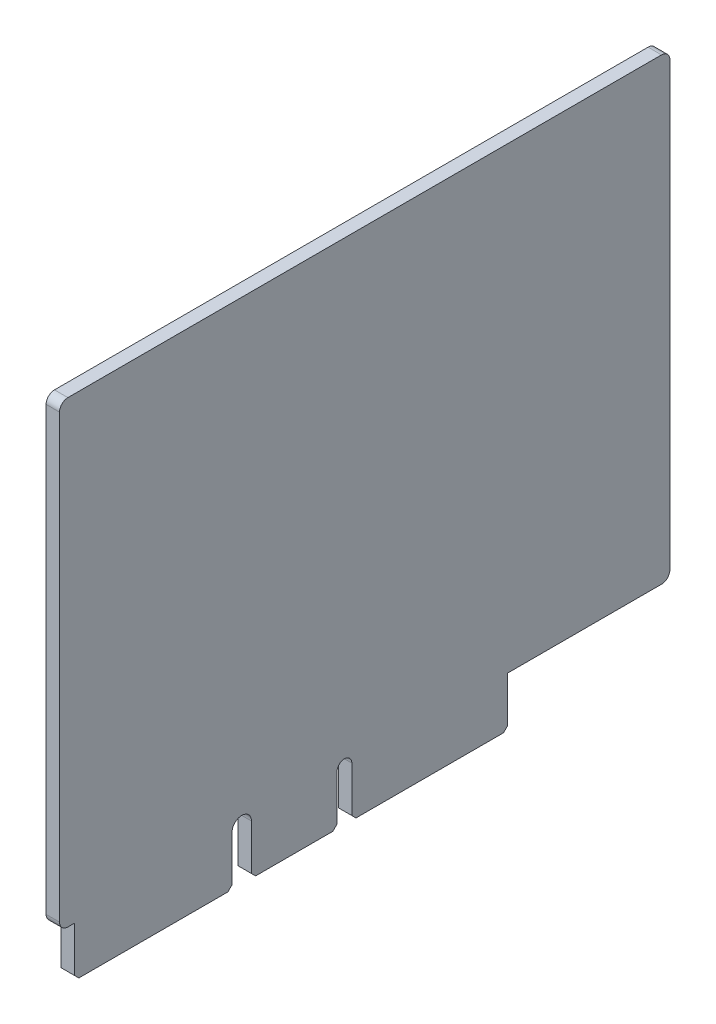
SolidWorks part; units mm, degrees
ref_plane "Front Plane" through (0, 0, 0) normal (0, 0, 1) x (1, 0, 0)
ref_plane "Top Plane" through (0, 0, 0) normal (0, 1, 0) x (1, 0, 0)
ref_plane "Right Plane" through (0, 0, 0) normal (1, 0, 0) x (0, 0, -1)
ref_plane "Plane1" through (23.8249, 0, 0) normal (1, 0, 0) x (0, 0, -1)
sketch "Sketch2" plane through (23.8249, 0, 0) normal (1, 0, 0) x (0, 0, -1)
  line L0 (-11.1377, 57.2752) -> (-31.2577, 57.2752) construction
  line L1 (-65.4077, 112.0173) -> (7.4736, 112.0173)
  line L2 (-65.4077, 112.0173) -> (-65.4077, 57.2752)
  line L3 (-65.4077, 57.2752) -> (-63.6027, 57.2752)
  line L4 (7.4736, 112.0173) -> (7.4736, 57.2752)
  line L5 (-44.8027, 57.2752) -> (-42.4927, 57.2752) construction
  line L6 (-32.2677, 57.2752) -> (-30.5077, 57.2752) construction
  line L7 (-11.8877, 57.2752) -> (7.4736, 57.2752)
  line L8 (-63.6027, 51.8452) -> (-63.1027, 51.3452)
  line L9 (-44.8027, 51.3452) -> (-44.8027, 56.5252)
  line L10 (-44.8027, 56.5252) -> (-63.6027, 56.5252)
  line L11 (-63.6027, 56.5252) -> (-63.6027, 51.3452)
  line L12 (-63.6027, 51.3452) -> (-44.8027, 51.3452)
  line L13 (-44.8027, 51.8452) -> (-44.8027, 57.2752)
  line L15 (-63.6027, 57.2752) -> (-63.6027, 51.8452)
  line L16 (-63.1027, 51.3452) -> (-45.3027, 51.3452)
  line L17 (-32.2677, 51.3452) -> (-32.2677, 56.5252)
  line L18 (-32.2677, 56.5252) -> (-42.4927, 56.5252)
  line L19 (-42.4927, 56.5252) -> (-42.4927, 51.3452)
  line L20 (-42.4927, 51.3452) -> (-32.2677, 51.3452)
  line L21 (-32.2677, 51.8452) -> (-32.2677, 57.2752)
  line L23 (-42.4927, 57.2752) -> (-42.4927, 51.8452)
  line L24 (-41.9927, 51.3452) -> (-32.7677, 51.3452)
  line L25 (-11.8877, 51.3452) -> (-11.8877, 56.5252)
  line L26 (-11.8877, 56.5252) -> (-30.5077, 56.5252)
  line L27 (-30.5077, 56.5252) -> (-30.5077, 51.3452)
  line L28 (-30.5077, 51.3452) -> (-11.8877, 51.3452)
  line L29 (-11.8877, 51.8452) -> (-11.8877, 57.2752)
  line L31 (-30.5077, 57.2752) -> (-30.5077, 51.8452)
  line L32 (-30.0077, 51.3452) -> (-12.3877, 51.3452)
  line L33 (-45.3027, 51.3452) -> (-44.8027, 51.8452)
  line L34 (-42.4927, 51.8452) -> (-41.9927, 51.3452)
  line L35 (-32.7677, 51.3452) -> (-32.2677, 51.8452)
  line L36 (-30.5077, 51.8452) -> (-30.0077, 51.3452)
  line L37 (-12.3877, 51.3452) -> (-11.8877, 51.8452)
  arc A0 (-42.4927, 57.2752) -> (-44.8027, 57.2752) centre (-43.6477, 57.2752) ccw
  arc A1 (-30.5077, 57.2752) -> (-32.2677, 57.2752) centre (-31.3877, 57.2752) ccw
  dimension "D1" = 0
  dimension "D2" = 0
  dimension "D3" = 0
extrude "Boss-Extrude1" add sketch "Sketch2" along normal blind 0.8 and the other way blind 0.8
fillet "Fillet1" radius 1 4 edges at (23.8249, 57.2752, 65.4077) (23.8249, 57.2752, -7.4736) (23.8249, 112.0173, -7.4736) (23.8249, 112.0173, 65.4077)
